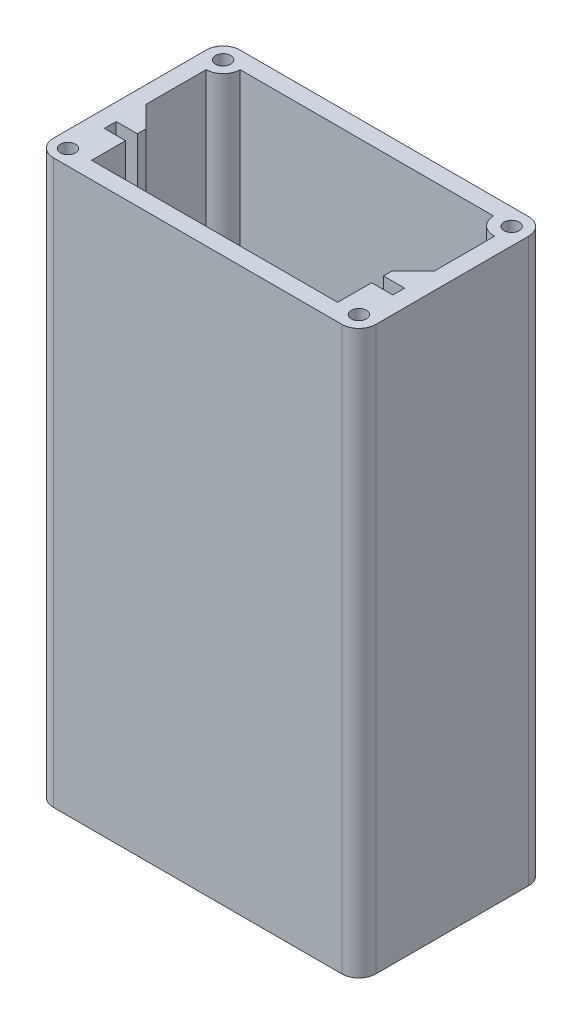
SolidWorks part; units mm, degrees
ref_plane "Front Plane" through (0, 0, 0) normal (0, 0, 1) x (1, 0, 0)
ref_plane "Top Plane" through (0, 0, 0) normal (0, 1, 0) x (1, 0, 0)
ref_plane "Right Plane" through (0, 0, 0) normal (1, 0, 0) x (0, 0, -1)
sketch "Sketch1" plane through (0, 0, 0) normal (0, 1, 0) x (1, 0, 0)
  line L1 (-24.13, -13.97) -> (24.13, -13.97)
  line L2 (-24.13, -13.97) -> (-24.13, 13.97)
  line L3 (-24.13, 13.97) -> (24.13, 13.97)
  line L4 (24.13, -13.97) -> (24.13, 13.97)
  line L5 (0, 13.97) -> (0, -13.97) construction
  line L6 (-24.13, 0) -> (24.13, 0) construction
  point P0 (0, 0)
  dimension "D1" = 48.26
  dimension "D2" = 27.94
extrude "Boss-Extrude1" add sketch "Sketch1" along normal blind 85.09
sketch "Sketch3" plane through (0, 85.09, 0) normal (0, 1, 0) x (1, 0, 0)
  line L11 (21.59, 0.508) -> (18.415, 0.508)
  line L12 (18.415, 0.508) -> (18.415, -4.572)
  line L20 (-19.05, 11.43) -> (18.8951, 11.43)
  line L21 (-21.59, 8.89) -> (-21.59, 0.508)
  line L22 (21.59, 8.8947) -> (21.59, 0.508)
  line L23 (-18.415, -6.35) -> (-18.415, -11.43)
  line L24 (-24.13, -13.97) -> (24.13, -13.97) construction
  line L25 (-18.415, -11.43) -> (18.415, -11.43)
  line L26 (18.415, -11.43) -> (18.415, -6.35)
  line L27 (18.415, -6.35) -> (21.59, -6.35)
  line L28 (-18.415, -6.35) -> (-21.59, -6.35)
  line L29 (-21.59, -6.35) -> (-21.59, -4.572)
  line L30 (-21.59, -4.572) -> (-18.415, -4.572)
  line L31 (-18.415, -4.572) -> (-18.415, 0.508)
  line L32 (-18.415, 0.508) -> (-21.59, 0.508)
  line L33 (21.59, -6.35) -> (21.59, -4.572)
  line L34 (21.59, -4.572) -> (18.415, -4.572)
  arc A0 (-21.59, 8.89) -> (-19.05, 11.43) centre (-21.59, 11.43) ccw
  arc A1 (18.8951, 11.43) -> (21.59, 8.8947) centre (21.4351, 11.43) ccw
  dimension "D1" = 2.54
  dimension "D2" = 5.08
  dimension "D3" = 1.778
  dimension "D4" = 5.08
  dimension "D6" = 3.175
  dimension "D9" = 43.0251
extrude "Cut-Extrude1" cut sketch "Sketch3" against normal offset from surface (82.55 mm away) 2.54 up to face at (0, 0, 0)
sketch "Sketch4" plane through (0, 2.54, 0) normal (0, 1, 0) x (1, 0, 0)
  line L1 (-8.255, -4.572) -> (8.255, -4.572)
  line L2 (-8.255, -4.572) -> (-8.255, 4.318)
  line L3 (-8.255, 4.318) -> (8.255, 4.318)
  line L4 (8.255, -4.572) -> (8.255, 4.318)
  line L5 (0, 4.318) -> (0, -4.572) construction
  line L6 (-8.255, -0.127) -> (8.255, -0.127) construction
  line L8 (-18.415, -4.572) -> (-21.59, -4.572) construction
  point P0 (0, -0.127)
  dimension "D1" = 16.51
  dimension "D2" = 8.89
hole_wizard "#43 (0.089) Diameter Hole1" positions "Sketch7" profile "Sketch8" hole size "#43" standard "ANSI Inch"
sketch "Sketch7" plane through (0, 85.09, 0) normal (0, 1, 0) x (1, 0, 0)
  line L0 (-24.13, 13.97) -> (-24.13, -13.97) construction
  line L1 (24.13, 13.97) -> (-24.13, 13.97) construction
  point P0 (-21.59, 11.43)
  point P2 (21.59, 11.43)
  point P4 (21.59, -11.43)
  point P6 (-21.7053, -11.6839)
  point P10 (0, 0)
  dimension "D1" = 43.18
  dimension "D2" = 22.86
  dimension "D3" = 2.54
  dimension "D4" = 2.54
sketch "Sketch8" plane through (-21.59, 85.09, -11.43) normal (1, 0, 0) x (0, 0, 1)
  line L0 (0, 0) -> (0, 19.7292)
  line L1 (0, 19.7292) -> (1.1303, 19.05)
  line L2 (1.1303, 19.05) -> (1.1303, 0)
  line L5 (1.1303, 0) -> (0, 0)
  line L10 (0, 19.7292) -> (-1.1303, 19.05) construction
  line L11 (0, -6.35) -> (0, 107.95) construction
  dimension "Hole Dia." = 2.2606
  dimension "Hole Depth" = 19.05
  dimension "Drill Angle" = 118
extrude "Cut-Extrude2" cut sketch "Sketch4" against normal through all
chamfer "Chamfer1" distance 3.81 angle 45 2 edges at (18.415, 43.815, -0.508) (-18.415, 43.815, -0.508)
fillet "Fillet1" radius 2.54 4 edges at (-24.13, 42.545, 13.97) (24.13, 42.545, 13.97) (24.13, 42.545, -13.97) (-24.13, 42.545, -13.97)
chamfer "Chamfer2" distance 1.27 angle 35 12 edges at (23.3861, 0, 13.2261) (24.13, 0, 0) (23.3861, 0, -13.2261) (0, 0, -13.97) (-23.3861, 0, -13.2261) (-24.13, 0, 0) (-23.3861, 0, 13.2261) (0, 0, 13.97) (0, 0, 4.572) (-8.255, 0, 0.127) (0, 0, -4.318) (8.255, 0, 0.127)
